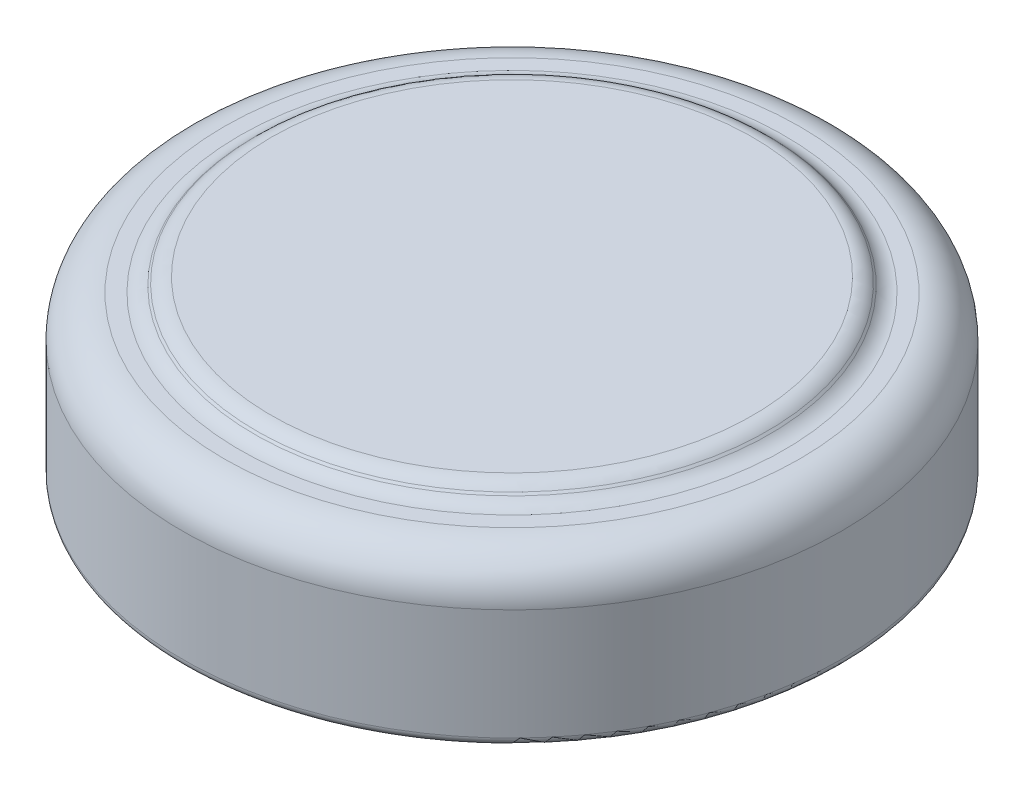
SolidWorks part; units mm, degrees
ref_plane "Front Plane" through (0, 0, 0) normal (0, 0, 1) x (1, 0, 0)
ref_plane "Top Plane" through (0, 0, 0) normal (0, 1, 0) x (1, 0, 0)
ref_plane "Right Plane" through (0, 0, 0) normal (1, 0, 0) x (0, 0, -1)
sketch "Sketch1" plane through (0, 0, 0) normal (0, 0, 1) x (1, 0, 0)
  line L0 (0, 0) -> (-3.85, 0)
  line L1 (-3.95, 0.1) -> (-3.95, 1.43)
  line L2 (-2.8864, 2.1) -> (0, 2.1)
  line L3 (0, 2.1) -> (0, 0)
  line L4 (-3.0632, 2.0268) -> (-3.0868, 2.0032)
  line L7 (-3.45, 1.93) -> (-3.2636, 1.93)
  arc A0 (-3.95, 1.43) -> (-3.45, 1.93) centre (-3.45, 1.43) cw
  arc A1 (-3.2636, 1.93) -> (-3.0868, 2.0032) centre (-3.2636, 2.18) ccw
  arc A2 (-2.8864, 2.1) -> (-3.0632, 2.0268) centre (-2.8864, 1.85) ccw
  arc A3 (-3.85, 0) -> (-3.95, 0.1) centre (-3.85, 0.1) cw
  point P9 (-3.95, 1.93)
  point P12 (-3.16, 1.93)
  point P14 (-2.99, 2.1)
  point P17 (-3.95, 0)
  dimension "D6" = 0.5
  dimension "D7" = 0.25
  dimension "D8" = 0.1
  dimension "D1" = 3.95
  dimension "D2" = 2.1
  dimension "D3" = 3.16
  dimension "D4" = 1.93
  dimension "D5" = 45
revolve "Revolve1" add sketch "Sketch1" angle 360 about L3
sketch "Sketch2" plane through (0, 0, 0) normal (0, -1, 0) x (1, 0, 0)
  line L0 (0.25, -0.25) -> (0.25, -1.5)
  line L1 (-0.25, 1.5) -> (0.25, 1.5)
  line L2 (-0.25, 1.5) -> (-0.25, 0.25)
  line L3 (-0.25, -1.5) -> (0.25, -1.5)
  line L4 (0.25, 1.5) -> (0.25, 0.25)
  line L5 (-1.5, 0.25) -> (-0.25, 0.25)
  line L6 (-1.5, 0.25) -> (-1.5, -0.25)
  line L7 (-1.5, -0.25) -> (-0.25, -0.25)
  line L8 (1.5, 0.25) -> (1.5, -0.25)
  line L9 (-0.25, -0.25) -> (-0.25, -1.5)
  line L10 (0.25, 0.25) -> (1.5, 0.25)
  line L11 (0.25, -0.25) -> (1.5, -0.25)
  circle A0 centre (0, 0) radius 2.5 construction
  text T0 "                    SR58" font "Century Gothic" height 1
  dimension "D1" = 5
  dimension "D2" = 0.5
  dimension "D3" = 0.25
  dimension "D4" = 0.25
  dimension "D5" = 0.5
  dimension "D6" = 3
  dimension "D7" = 1.5
  dimension "D8" = 1.5
  dimension "D9" = 3
wrap "Wrap1" sketch "Sketch2" wrap type scribe source sketch "Sketch2" face at (-3.85, 0, 0)
